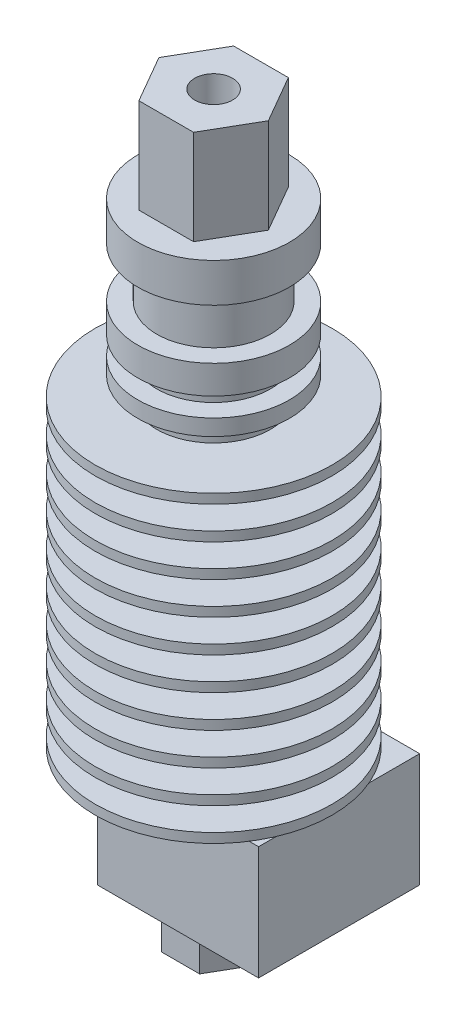
SolidWorks part; units mm, degrees
material "6061 Alloy"
ref_plane "Front Plane" through (0, 0, 0) normal (0, 0, 1) x (1, 0, 0)
ref_plane "Top Plane" through (0, 0, 0) normal (0, 1, 0) x (1, 0, 0)
ref_plane "Right Plane" through (0, 0, 0) normal (1, 0, 0) x (0, 0, -1)
sketch "Sketch1" plane through (0, 0, 0) normal (0, 0, 1) x (1, 0, 0)
  line L0 (0, 0) -> (0, 61.158) construction
  line L1 (1, 0) -> (12.5, 0)
  line L2 (12.5, 0) -> (12.5, 1)
  line L3 (12.5, 1) -> (8, 1)
  line L4 (8, 1) -> (8, 3.4444)
  line L5 (8, 3.4444) -> (12.5, 3.4444)
  line L6 (12.5, 3.4444) -> (12.5, 4.4444)
  line L7 (12.5, 4.4444) -> (8, 4.4444)
  line L8 (8, 4.4444) -> (8, 6.8889)
  line L9 (8, 6.8889) -> (12.5, 6.8889)
  line L10 (12.5, 6.8889) -> (12.5, 7.8889)
  line L11 (12.5, 7.8889) -> (8, 7.8889)
  line L12 (8, 7.8889) -> (8, 10.3333)
  line L13 (8, 10.3333) -> (12.5, 10.3333)
  line L14 (12.5, 10.3333) -> (12.5, 11.3333)
  line L15 (12.5, 11.3333) -> (8, 11.3333)
  line L16 (8, 11.3333) -> (8, 13.7778)
  line L17 (8, 13.7778) -> (12.5, 13.7778)
  line L18 (12.5, 13.7778) -> (12.5, 14.7778)
  line L19 (12.5, 14.7778) -> (8, 14.7778)
  line L20 (8, 14.7778) -> (8, 17.2222)
  line L21 (8, 17.2222) -> (12.5, 17.2222)
  line L22 (12.5, 17.2222) -> (12.5, 18.2222)
  line L23 (12.5, 18.2222) -> (8, 18.2222)
  line L24 (8, 18.2222) -> (8, 20.6667)
  line L25 (8, 20.6667) -> (12.5, 20.6667)
  line L26 (12.5, 20.6667) -> (12.5, 21.6667)
  line L27 (12.5, 21.6667) -> (8, 21.6667)
  line L28 (8, 21.6667) -> (8, 24.1111)
  line L29 (8, 24.1111) -> (12.5, 24.1111)
  line L30 (12.5, 24.1111) -> (12.5, 25.1111)
  line L31 (12.5, 25.1111) -> (8, 25.1111)
  line L32 (8, 25.1111) -> (8, 27.5556)
  line L33 (8, 27.5556) -> (12.5, 27.5556)
  line L34 (12.5, 27.5556) -> (12.5, 28.5556)
  line L35 (12.5, 28.5556) -> (8, 28.5556)
  line L36 (8, 28.5556) -> (8, 31)
  line L37 (8, 31) -> (12.5, 31)
  line L38 (12.5, 31) -> (12.5, 32)
  line L39 (12.5, 32) -> (6, 32)
  line L41 (6, 32) -> (6, 34)
  line L42 (6, 34) -> (8, 34)
  line L43 (8, 34) -> (8, 35.7)
  line L44 (8, 35.7) -> (6, 35.7)
  line L45 (6, 35.7) -> (6, 37.7)
  line L46 (6, 37.7) -> (8, 37.7)
  line L47 (8, 37.7) -> (8, 40.7)
  line L48 (8, 40.7) -> (6, 40.7)
  line L49 (6, 40.7) -> (6, 46)
  line L50 (6, 46) -> (8, 46)
  line L51 (8, 46) -> (8, 50.1)
  line L52 (8, 50.1) -> (1, 50.1)
  line L54 (1, 50.1) -> (1, 0)
  dimension "D1" = 32
  dimension "D2" = 1
  dimension "D3" = 12.5
  dimension "D4" = 1
  dimension "D5" = 7
  dimension "D6" = 8
  dimension "D7" = 6
  dimension "D8" = 14
  dimension "D9" = 4.1
  dimension "D10" = 3
  dimension "D11" = 5.3
  dimension "D12" = 2
  dimension "D13" = 2
revolve "Revolve1" add sketch "Sketch1" angle 360 about L0
sketch "Sketch2" plane through (0, 0, 0) normal (0, -1, 0) x (1, 0, 0)
  circle A0 centre (0, 0) radius 1.7927
  circle A1 centre (0, 0) radius 1 construction
  circle A2 centre (0, 0) radius 1
extrude "Boss-Extrude1" add sketch "Sketch2" along normal blind 3
sketch "Sketch3" plane through (0, -3, 0) normal (0, -1, 0) x (1, 0, 0)
  line L1 (-8.5, -13.2422) -> (8.5, -13.2422)
  line L2 (-8.5, -13.2422) -> (-8.5, 3.7578)
  line L3 (-8.5, 3.7578) -> (8.5, 3.7578)
  line L4 (8.5, -13.2422) -> (8.5, 3.7578)
  circle A0 centre (0, 0) radius 1 construction
  circle A1 centre (0, 0) radius 1
  point P7 (0, 3.7578)
  dimension "D1" = 17
extrude "Boss-Extrude2" add sketch "Sketch3" along normal blind 12 separate body
sketch "Sketch4" plane through (0, -15, 0) normal (0, -1, 0) x (1, 0, 0)
  line L1 (2.0207, 3.5) -> (-2.0207, 3.5)
  line L2 (-2.0207, 3.5) -> (-4.0415, 0)
  line L3 (-4.0415, 0) -> (-2.0207, -3.5)
  line L4 (-2.0207, -3.5) -> (2.0207, -3.5)
  line L5 (2.0207, -3.5) -> (4.0415, 0)
  line L6 (4.0415, 0) -> (2.0207, 3.5)
  circle A0 centre (0, 0) radius 3.5 construction
  circle A1 centre (0, 0) radius 1 construction
  circle A2 centre (0, 0) radius 1
  dimension "D1" = 7
extrude "Boss-Extrude3" add sketch "Sketch4" along normal blind 3
sketch "Sketch5" plane through (0, 0, 0) normal (0, 0, 1) x (1, 0, 0)
  line L0 (0, 0) -> (0, -22.864) construction
  line L1 (0.2, -18) -> (0.2, -20)
  line L2 (2.0207, -18) -> (-2.0207, -18) construction
  line L3 (0.2, -20) -> (2.9453, -18)
  line L4 (4.0415, -18) -> (2.0207, -18) construction
  line L5 (2.9453, -18) -> (0.2, -18)
  dimension "D1" = 2
  dimension "D2" = 0.2
revolve "Revolve2" add sketch "Sketch5" angle 360 about L0
sketch "Sketch6" plane through (8.5, 0, 0) normal (1, 0, 0) x (0, 0, -1)
  circle A0 centre (7.4507, -8.9214) radius 2.5
  circle A1 centre (10.5916, -13.2255) radius 0.7357
  dimension "D1" = 5
extrude "Cut-Extrude1" [suppressed] cut sketch "Sketch6" against normal through all
sketch "Sketch8" plane through (0, 50.1, 0) normal (0, 1, 0) x (1, 0, 0)
  line L1 (2.8868, 5) -> (-2.8868, 5)
  line L2 (-2.8868, 5) -> (-5.7735, 0)
  line L3 (-5.7735, 0) -> (-2.8868, -5)
  line L4 (-2.8868, -5) -> (2.8868, -5)
  line L5 (2.8868, -5) -> (5.7735, 0)
  line L6 (5.7735, 0) -> (2.8868, 5)
  circle A0 centre (0, 0) radius 5 construction
  circle A1 centre (0, 0) radius 2
  dimension "D2" = 4
  dimension "D1" = 10
extrude "Boss-Extrude4" add sketch "Sketch8" along normal blind 10
sketch "Sketch9" [suppressed] plane through (8.5, 0, 0) normal (1, 0, 0) x (0, 0, -1)
  circle A0 centre (7.4507, -8.9214) radius 2.5 construction
  circle A1 centre (7.4507, -8.9214) radius 2.5
extrude "Boss-Extrude5" [suppressed] add sketch "Sketch9" along normal blind 4 and the other way blind 15
ref_plane "Plane1" through (0, 0, -7.2422) normal (0, 0, -1) x (-1, 0, 0)
